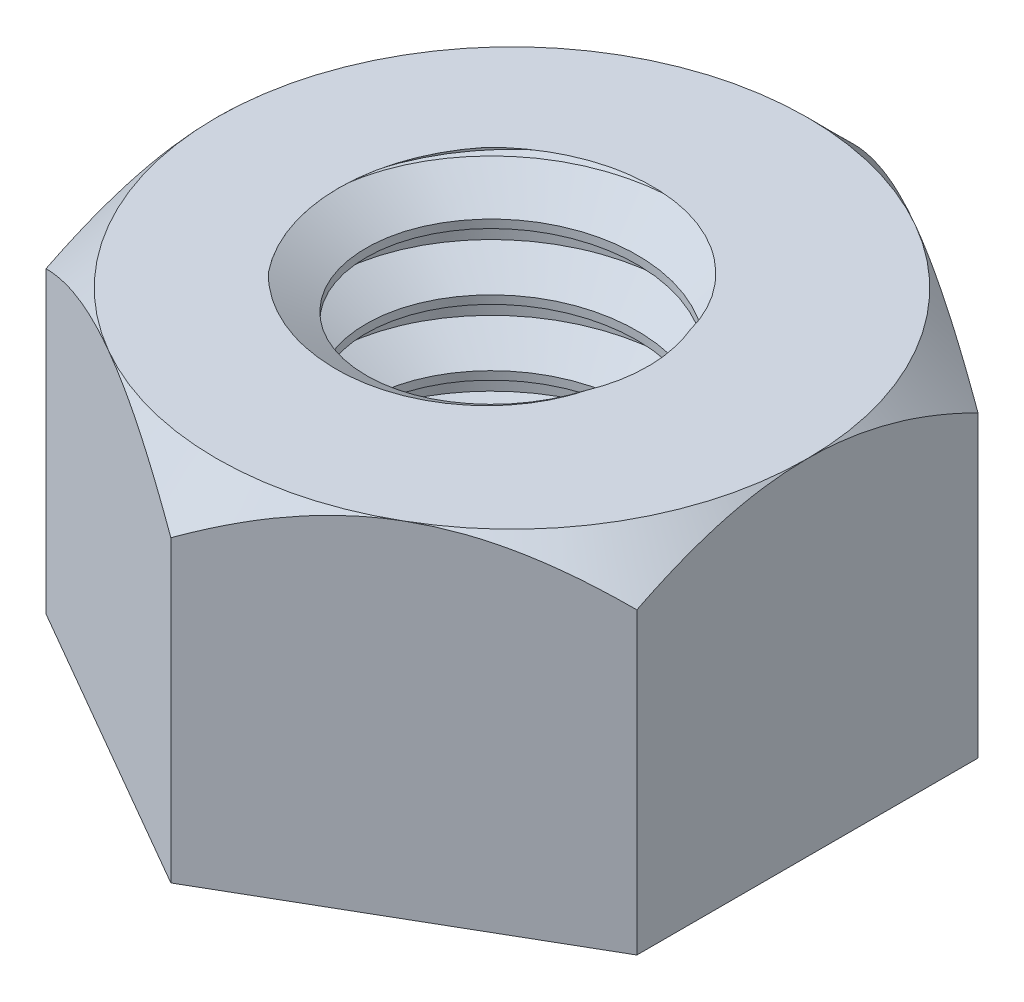
SolidWorks part; units mm, degrees
note: '?' marks a value the reader was unsure of. The reader was unsure of these and kept them because the rebuilt part matched: shared geometry of "Sketch6<2>", "Sketch1<2>".
ref_plane "Front" through (0, 0, 0) normal (0, 0, 1) x (1, 0, 0)
ref_plane "Top" through (0, 0, 0) normal (0, 1, 0) x (1, 0, 0)
ref_plane "Right" through (0, 0, 0) normal (1, 0, 0) x (0, 0, -1)
sketch "Sketch1" plane through (0, 0, 0) normal (0, 1, 0) x (1, 0, 0)
  line L1 (0, 8.2489) -> (-7.1438, 4.1244)
  line L2 (-7.1438, 4.1244) -> (-7.1438, -4.1244)
  line L3 (-7.1438, -4.1244) -> (0, -8.2489)
  line L4 (0, -8.2489) -> (7.1437, -4.1244)
  line L5 (7.1437, -4.1244) -> (7.1437, 4.1244)
  line L6 (7.1437, 4.1244) -> (0, 8.2489)
  circle A0 centre (0, 0) radius 7.1438 construction
  dimension "Hex Flats" = 14.2875
extrude "Extrude1" add sketch "Sketch1" along normal blind 8.3344
sketch "Sketch3" plane through (0, 0, 0) normal (1, 0, 0) x (0, 0, -1)
  line L0 (7.1437, 8.3344) -> (8.2489, 7.2292)
  line L1 (4.1244, 8.3344) -> (8.2489, 8.3344) construction
  line L2 (8.2489, 8.3344) -> (8.2489, 0) construction
  line L3 (8.2489, 7.2292) -> (8.2489, 8.3344)
  line L4 (8.2489, 8.3344) -> (7.1437, 8.3344)
  line L5 (0, 0.542) -> (0, -0.542) construction
  dimension "D1" = 45
  dimension "D2" = 14.2875
revolve "Cut-Revolve2" cut sketch "Sketch3" angle 360 about L5
sketch "Sketch2" plane through (0, 0, 0) normal (0, 0, 1) x (1, 0, 0)
  line L0 (0, 1.6636) -> (0, -0.3796) construction
  line L1 (0, 8.3344) -> (4.1897, 8.3344)
  line L3 (0, 8.3344) -> (7.1437, 8.3344) construction
  line L4 (0, 7.276) -> (4.1897, 7.276)
  line L5 (4.1897, 8.3344) -> (4.7625, 8.0036)
  line L6 (4.7625, 8.0036) -> (4.7625, 7.8714)
  line L7 (4.7625, 7.8714) -> (4.1897, 7.5406)
  line L9 (4.1897, 7.276) -> (4.1897, 7.5406)
  line L10 (0, 7.276) -> (0, 8.3344)
  line L11 (4.1897, 8.3344) -> (4.1897, 7.5406) construction
  line L12 (4.7625, 7.9375) -> (4.1897, 7.9375) construction
  dimension "D1" = 60
  dimension "D2" = 0.2646
  dimension "D5" = 0.1323
  dimension "Pitch" = 1.0583
  dimension "Major Dia." = 9.525
revolve "Cut-Revolve1" cut sketch "Sketch2" angle 360 about L0
ref_point "Point1"
ref_axis "Axis1" through (0, 7.276, 0) along (0, 1, 0)?
sketch "Sketch6" plane through (0, 0, 0) normal (0, 1, 0) x (1, 0, 0)
  circle A0 centre (0, 0) radius 4.191
  dimension "D1" = 8.382
curve "Helix/Spiral1" pitch 1.5875 height 12.7 turns 8
ref_axis "Axis2" through (0, 0, -8.2489) along (0, 0, 1)?
ref_point "Point2"
extrude "Cut-Extrude1" cut sketch "Sketch6<2>" along normal through all
sketch "Sketch6<2>" plane through (0, 0, 0) normal (0, 1, 0) x (1, 0, 0) same geometry as "Sketch6"
sketch "Sketch11" plane through (0, 0, 0) normal (1, 0, 0) x (0, 1, 0)
  line L0 (0.0992, 3.2867) -> (-0.0992, 3.2867)
  line L1 (-0.0992, 3.2867) -> (-0.6945, 4.3178)
  line L2 (0.0992, 3.2867) -> (0.6945, 4.3178)
  line L3 (0.6945, 4.3178) -> (-0.6945, 4.3178)
  line L4 (0, 8.0492) -> (0, 3.2867) construction
  line L5 (0.3969, 3.8022) -> (-0.3969, 3.8022) construction
  point P0 (0.1321, -4.1889)
  dimension "D1" = 4.191
  dimension "D2" = 60
  dimension "D3" = 30
  dimension "D4" = 0.1984
  dimension "D5" = 0.7937
sweep "Sweep3" add profiles "Sketch11" path "Helix/Spiral1"
extrude "Cut-Extrude2" cut sketch "Sketch1<2>" against normal blind 2.54
sketch "Sketch1<2>" plane through (0, 0, 0) normal (0, 1, 0) x (1, 0, 0) same geometry as "Sketch1"
sketch "Sketch12" plane through (0, 8.3344, 0) normal (0, 1, 0) x (1, 0, 0)
  circle A0 centre (0, 0) radius 5.1039
extrude "Cut-Extrude3" cut sketch "Sketch12" along normal through all
equation "\"D5@Sketch2\"=\"Pitch@Sketch2\"/8"
equation "\"D2@Sketch2\"=\"Pitch@Sketch2\"/4"
equation "\"D2@Sketch3\"= \"Hex Flats@Sketch1\""
